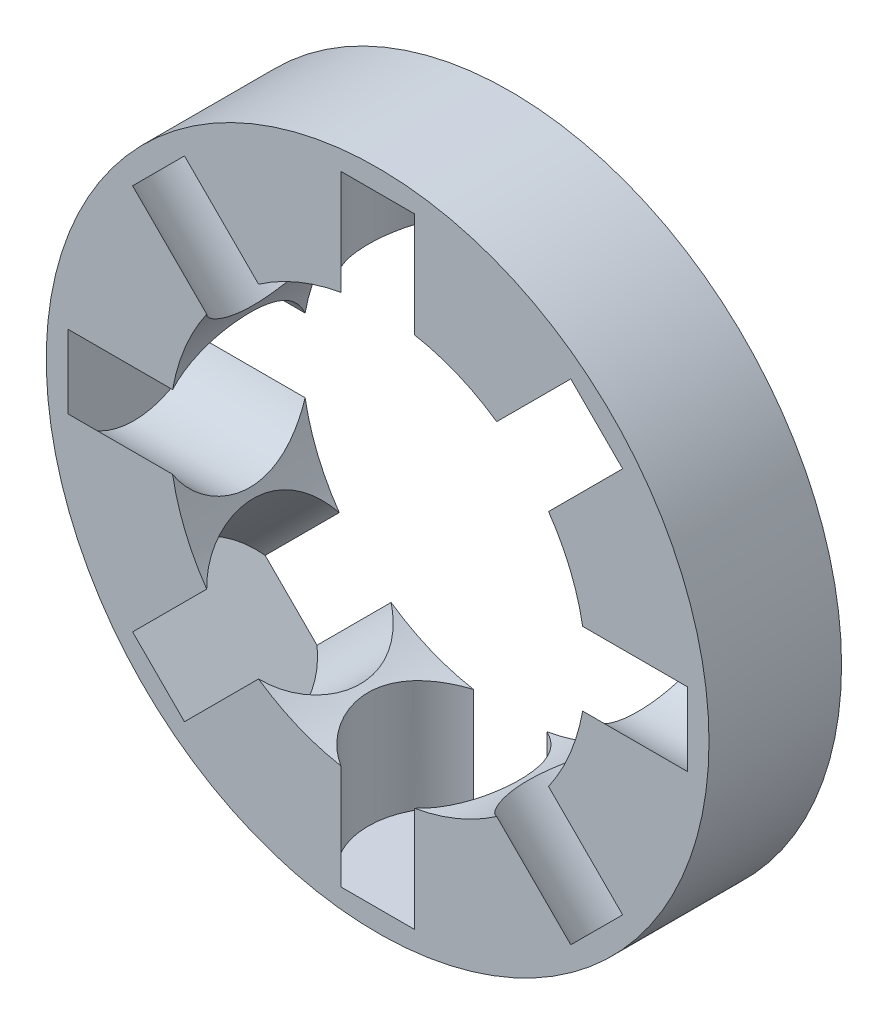
SolidWorks part; units mm, degrees
ref_plane "Top Plane" through (0, 0, 0) normal (0, 0, 1) x (1, 0, 0)
ref_plane "Right Plane" through (0, 0, 0) normal (0, 1, 0) x (1, 0, 0)
ref_plane "Front Plane" through (0, 0, 0) normal (1, 0, 0) x (0, 0, -1)
ref_axis "x-axis" through (-88.99, 0, 0) along (1, 0, 0)
ref_axis "y-axis" through (0, -55, 0) along (0, 1, 0)
ref_axis "z-axis" through (0, 0, 55) along (0, 0, -1)
sketch "Sketch1" plane through (0, 0, 0) normal (0, 0, 1) x (1, 0, 0)
  circle A0 centre (0, 0) radius 11
  circle A1 centre (0, 0) radius 17.5
  dimension "D1" = 22
  dimension "D2" = 6.5
extrude "Boss-Extrude1" add sketch "Sketch1" along normal mid plane 7
sketch "Sketch3" plane through (0, 0, 0) normal (0, 0, 1) x (1, 0, 0)
  line L0 (10.1627, -4.2095) -> (10.1627, 4.2095) construction
  line L1 (-10.1627, 4.2095) -> (-10.1627, -4.2095) construction
  line L2 (-10.1627, -4.2095) -> (-4.2095, -10.1627) construction
  line L3 (-4.2095, -10.1627) -> (4.2095, -10.1627) construction
  line L4 (4.2095, -10.1627) -> (10.1627, -4.2095) construction
  line L5 (10.1627, 4.2095) -> (4.2095, 10.1627) construction
  line L6 (4.2095, 10.1627) -> (-4.2095, 10.1627) construction
  line L7 (-4.2095, 10.1627) -> (-10.1627, 4.2095) construction
  line L8 (0, -55) -> (0, 55) construction
  circle A0 centre (0, 0) radius 10.1627 construction
  circle A2 centre (0, 0) radius 11 construction
  point P15 (0, 10.1627)
ref_plane "Plane1" through (-10.1627, 0, 0) normal (1, 0, 0) x (0, 0, -1)
sketch "Sketch4" plane through (-10.1627, 0, 0) normal (1, 0, 0) x (0, 0, -1)
  line L0 (0, 4.2095) -> (0, -4.2095) construction
  circle A0 centre (0, 0) radius 4
  dimension "D1" = 8
extrude "Cut-Extrude1" cut sketch "Sketch4" against normal blind 6.2
pattern_circular "CirPattern1" count 8 over 360 about axis through (0, 0, 3.5) along (0, 0, -1) of "Cut-Extrude1"
